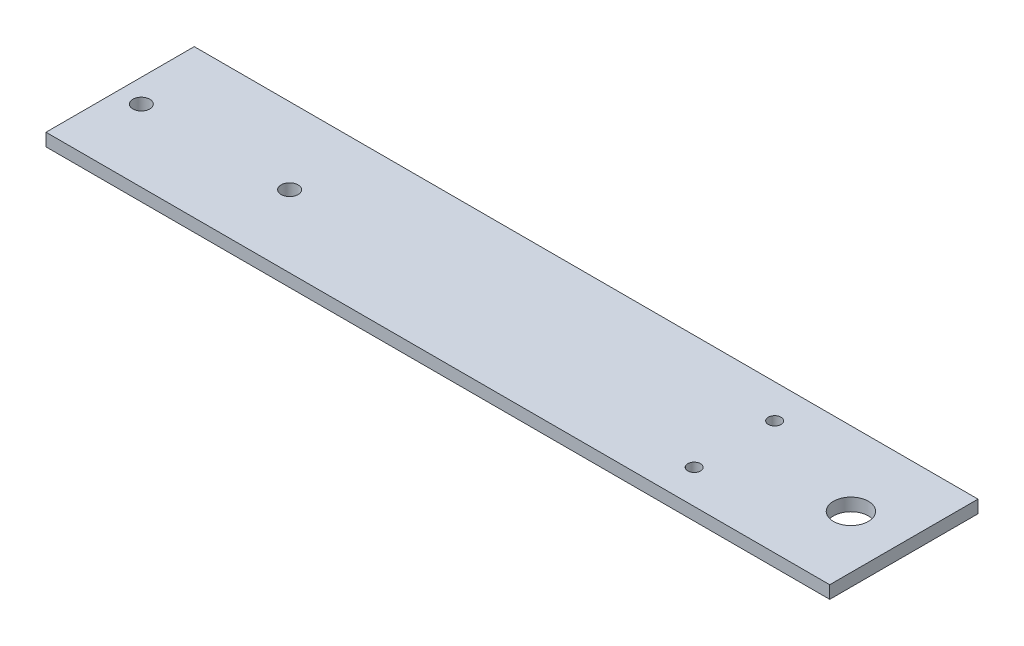
SolidWorks part; units mm, degrees
ref_plane "Front Plane" through (0, 0, 0) normal (0, 0, 1) x (1, 0, 0)
ref_plane "Top Plane" through (0, 0, 0) normal (0, 1, 0) x (1, 0, 0)
ref_plane "Right Plane" through (0, 0, 0) normal (1, 0, 0) x (0, 0, -1)
sketch "Sketch1" plane through (0, 0, 0) normal (0, 1, 0) x (1, 0, 0)
  line L1 (-92.5, 17.5) -> (92.5, 17.5)
  line L2 (-92.5, 17.5) -> (-92.5, -17.5)
  line L3 (-92.5, -17.5) -> (92.5, -17.5)
  line L4 (92.5, 17.5) -> (92.5, -17.5)
  line L5 (-92.5, 17.5) -> (92.5, -17.5) construction
  line L6 (-92.5, -17.5) -> (92.5, 17.5) construction
  circle A0 centre (-10.6801, 3.3392) radius 4.5
  circle A1 centre (-10.6585, -3.6607) radius 14
  circle A2 centre (-28.1585, -4.7634) radius 2
  circle A3 centre (6.8415, -4.7634) radius 2
  circle A4 centre (80, 0) radius 4.125
  point P0 (0, 0)
  point P17 (92.5, 0)
  dimension "D3" = 12.5
  dimension "D4" = 4
  dimension "D5" = 4
  dimension "D6" = 8.25
  dimension "D1" = 35
  dimension "D2" = 185
  dimension "D7" = 8.1025
  dimension "D8" = 8.1025
  dimension "D9" = 17.5
extrude "Boss-Extrude1" add sketch "Sketch1" along normal blind 3 contours A1 L3 L4 L1 L2 A4 A3 A2 | L3 A1 A0 | A2 | A3 | A0 region at (0, 0, -15.6172) region at (-10.656, 0, 4.4565) region at (-28.1585, 0, 4.7634) region at (6.8415, 0, 4.7634)
sketch "Sketch2" plane through (0, 3, 0) normal (0, 1, 0) x (1, 0, 0)
  line L0 (-92.5, 17.5) -> (-92.5, -17.5) construction
  line L1 (-92.5, -17.5) -> (92.5, -17.5) construction
  line L2 (-69.5, 6.5) -> (-69.5, -6.7467) construction
  circle A0 centre (-69.5, 6.5) radius 3
  circle A1 centre (-69.5, 6.5) radius 15 construction
  circle A2 centre (-27, 6.5) radius 27.5 construction
  circle A3 centre (-87, -0.5) radius 2
  circle A4 centre (-52, -0.5) radius 2
  dimension "D1" = 6
  dimension "D3" = 24
  dimension "D4" = 7
  dimension "D2" = 23
  dimension "D5" = 17.5
extrude "Cut-Extrude1" cut sketch "Sketch2" against normal through all contours A3 | A4
sketch "Sketch3" plane through (0, 3, 0) normal (0, 1, 0) x (1, 0, 0)
  line L0 (-92.5, -17.5) -> (92.5, -17.5) construction
  line L3 (92.5, 17.5) -> (92.5, -17.5) construction
  line L4 (-1.65, 0) -> (1.65, 0) construction
  circle A0 centre (72.5, -9.5) radius 1.5
  circle A3 centre (72.5, 9.5) radius 1.5
  point P4 (75.429, -6.5655)
  point P7 (92.5, -9.1098)
  dimension "D1" = 3
  dimension "D2" = 8
  dimension "D3" = 20
extrude "Cut-Extrude2" [suppressed] cut sketch "Sketch3" against normal through all
sketch "Sketch4" plane through (0, 3, 0) normal (0, 1, 0) x (1, 0, 0)
  line L0 (-92.5, 17.5) -> (92.5, 17.5) construction
  line L1 (80, 0) -> (59, 0) construction
  line L2 (92.5, 17.5) -> (92.5, -17.5) construction
  line L3 (-1.65, 0) -> (1.65, 0) construction
  circle A1 centre (52.5, 9.5) radius 1.5
  circle A2 centre (52.5, -9.5) radius 1.5
  dimension "D2" = 8
  dimension "D4" = 3
  dimension "D1" = 21
  dimension "D3" = 40
extrude "Cut-Extrude3" cut sketch "Sketch4" against normal through all
